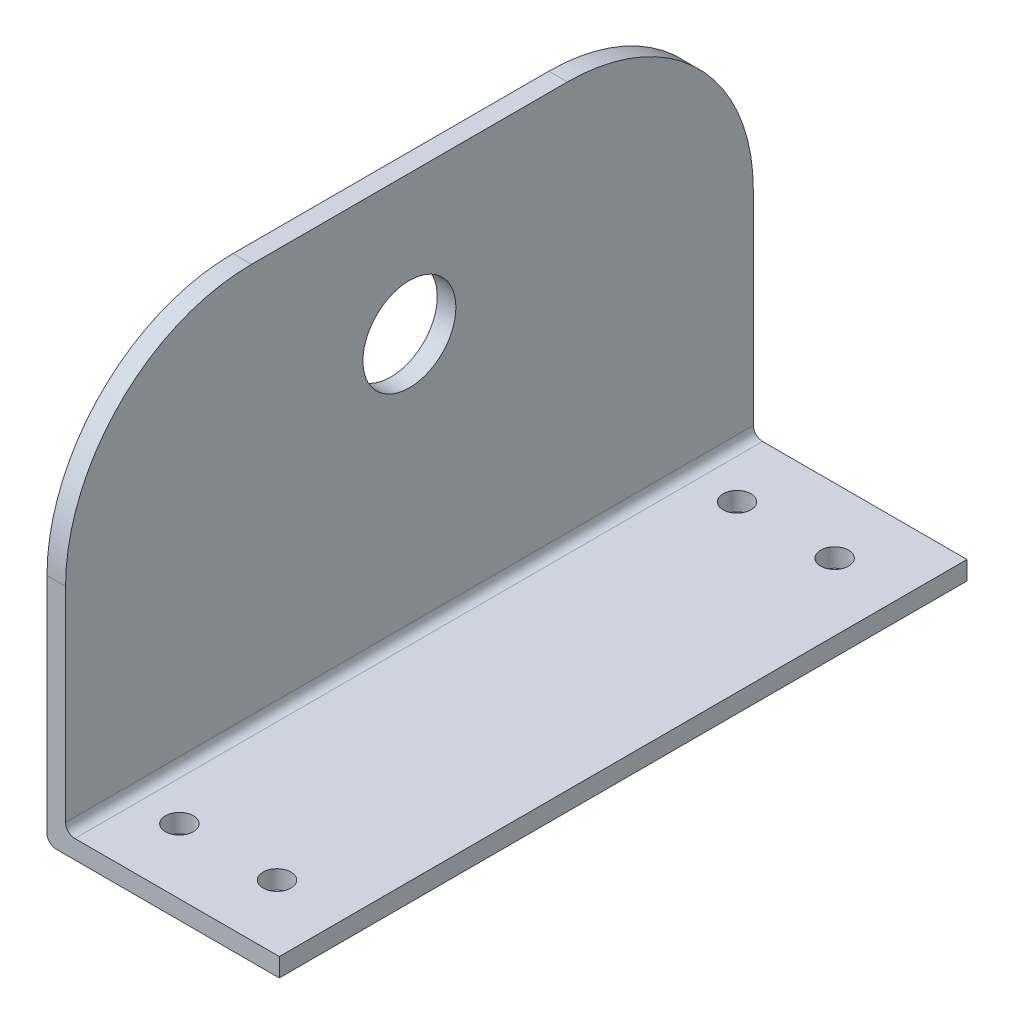
SolidWorks part; units mm, degrees
ref_plane "Front Plane" through (0, 0, 0) normal (0, 0, 1) x (1, 0, 0)
ref_plane "Top Plane" through (0, 0, 0) normal (0, 1, 0) x (1, 0, 0)
ref_plane "Right Plane" through (0, 0, 0) normal (1, 0, 0) x (0, 0, -1)
sketch "Sketch1" plane through (0, 0, 0) normal (0, 1, 0) x (1, 0, 0)
  line L0 (2, 74) -> (2, 0)
  line L1 (0, 0) -> (25, 0)
  line L2 (0, 0) -> (0, 74)
  line L3 (0, 74) -> (25, 74)
  line L4 (25, 0) -> (25, 74)
  line L5 (12.5, 74) -> (12.5, 0) construction
  line L6 (0, 37) -> (25, 37) construction
  circle A0 centre (17.75, 67) radius 1.5
  circle A1 centre (7.25, 67) radius 1.5
  circle A2 centre (17.75, 7) radius 1.5
  circle A3 centre (7.25, 7) radius 1.5
  dimension "D4" = 3
  dimension "D1" = 25
  dimension "D2" = 74
  dimension "D3" = 2
  dimension "D5" = 10.5
  dimension "D6" = 60
extrude "Boss-Extrude1" add sketch "Sketch1" along normal blind 2 contours L1 L4 L3 L0 region at (13.5169, 0, -37)
extrude "Boss-Extrude2" add sketch "Sketch1<3>" along normal blind 45 contours L3 L2 L1 L0 region at (1, 0, -37)
sketch "Sketch1<3>" plane through (0, 0, 0) normal (0, 1, 0) x (1, 0, 0) same geometry as "Sketch1"
fillet "Fillet1" radius 1 2 edges at (2, 2, -37) (0, 0, -37)
fillet "Fillet2" radius 20 2 edges at (1, 45, -74) (1, 45, 0)
sketch "Sketch2" plane through (0, 0, 0) normal (-1, 0, 0) x (0, 0, 1)
  line L0 (-37, 45) -> (-37, 1) construction
  line L1 (-20, 45) -> (-54, 45) construction
  line L2 (-74, 1) -> (0, 1) construction
  circle A0 centre (-37, 30) radius 5
  dimension "D1" = 10
  dimension "D2" = 15
extrude "Cut-Extrude1" cut sketch "Sketch2" against normal up to surface (2 mm away) up to face at (2, 25.714, -37)
